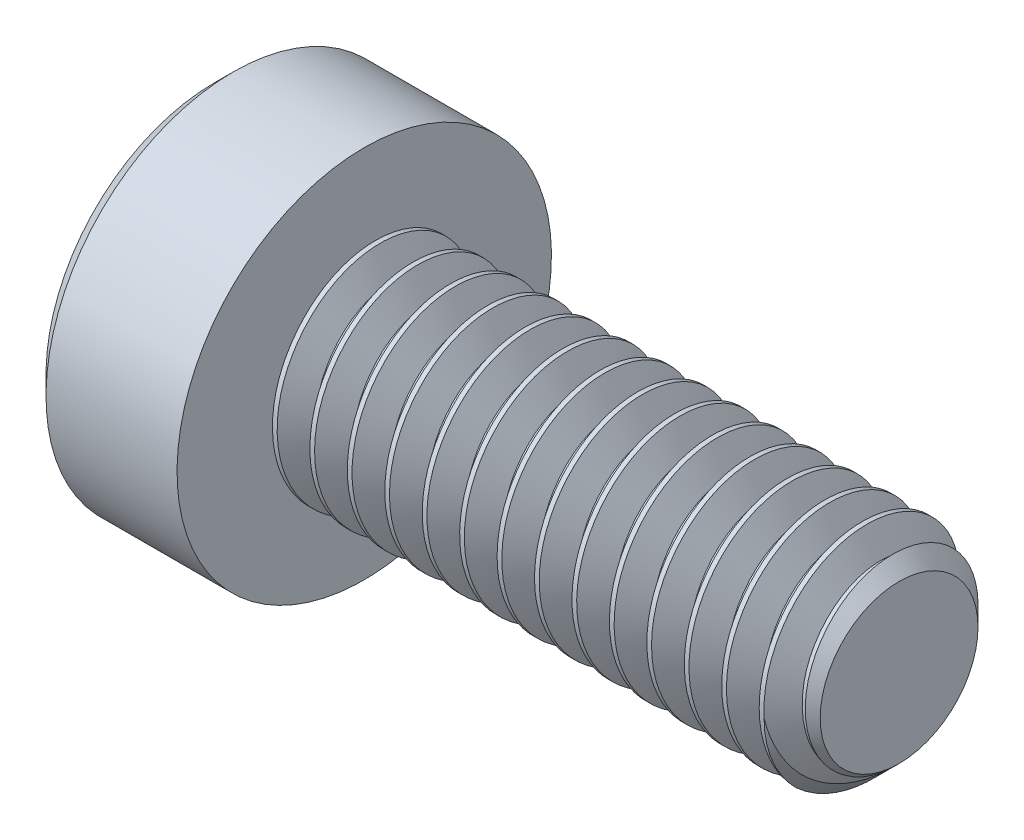
SolidWorks part; units mm, degrees
ref_plane "Front Plane" through (0, 0, 0) normal (0, 0, 1) x (1, 0, 0)
ref_plane "Top Plane" through (0, 0, 0) normal (0, 1, 0) x (1, 0, 0)
ref_plane "Right Plane" through (0, 0, 0) normal (1, 0, 0) x (0, 0, -1)
sketch "Sketch1" plane through (0, 0, 0) normal (0, 0, 1) x (1, 0, 0)
  line L0 (5, 0) -> (-5, 0) construction
  line L1 (5, 2) -> (5, -2) construction
  line L2 (-5, 3.5) -> (-5, -3.5) construction
  line L3 (-5, 3.5) -> (-7.45, 3.5) construction
  line L4 (-7.45, 3.5) -> (-7.8, 3.15) construction
  line L5 (-7.8, 3.15) -> (-7.8, -3.15) construction
  line L6 (-7.8, -3.15) -> (-7.45, -3.5) construction
  line L7 (-7.45, -3.5) -> (-5, -3.5) construction
  point P7 (-5.38, 0)
  point P12 (2.2, -2)
  dimension "D1" = 45
  dimension "Dec." = 4
  dimension "Length" = 10
  dimension "Head Dia" = 7
  dimension "Head Height" = 2.8
  dimension "Hex Depth" = 2.42
  dimension "Chamfer" = 0.35
  dimension "D2" = 2.8
ref_plane "Plane1" through (5, 0, 0) normal (1, 0, 0) x (0, 0, -1)
ref_plane "Plane2" through (-7.8, 0, 0) normal (1, 0, 0) x (0, 0, -1)
sketch "Sketch2" plane through (5, 0, 0) normal (1, 0, 0) x (0, 0, -1)
  circle A0 centre (0, 0) radius 2
extrude "Boss-Extrude1" add sketch "Sketch2" against normal up to vertex (10 mm away) up to point (-5, 0, 0)
sketch "Sketch3" plane through (5, 0, 0) normal (1, 0, 0) x (0, 0, -1)
  circle A0 centre (0, 0) radius 2 construction
  circle A1 centre (0, 0) radius 2
curve "Helix/Spiral1" pitch 0.7 height 10.67 radius 2 centre (5, 0, 0) axis (-1, 0, 0) start towards (0, 1, 0) parameters "Pitch"=0.7
chamfer "Chamfer1" distance 0.525 angle 45 1 edges at (5, 0, -2)
sketch "Sketch5" plane through (0, 0, 0) normal (0, 0, 1) x (1, 0, 0)
  line L0 (5, 2) -> (5.6125, 2)
  line L1 (5.6125, 2) -> (5.35, 1.5453)
  line L2 (5.35, 1.5453) -> (5.2625, 1.5453)
  line L3 (5.2625, 1.5453) -> (5, 2)
  line L4 (5.3063, 1.5453) -> (5.3063, 2) construction
  line L5 (5.1313, 1.7727) -> (5.4813, 1.7727) construction
  dimension "D1" = 60
  dimension "D2" = 0.35
  dimension "D3" = 0.0875
sweep "Cut-Sweep1" cut profiles "Sketch5" path "Helix/Spiral1" align with end faces yes
sketch "Sketch4" plane through (-7.8, 0, 0) normal (1, 0, 0) x (0, 0, -1)
  line L0 (-3.5, 0.7937) -> (3.5, 0.7937) construction
  line L1 (0, 1.4434) -> (-1.25, 0.7217)
  line L2 (-1.25, 0.7217) -> (-1.25, -0.7217)
  line L3 (-1.25, -0.7217) -> (0, -1.4434)
  line L4 (0, -1.4434) -> (1.25, -0.7217)
  line L5 (1.25, -0.7217) -> (1.25, 0.7217)
  line L6 (1.25, 0.7217) -> (0, 1.4434)
  line L7 (0, 0) -> (0, 0.7937) construction
  circle A0 centre (0, 0) radius 1.25 construction
  dimension "Hex Size" = 2.5
  dimension "D1" = 7
  dimension "D2" = 0.7937
sketch "Sketch6" plane through (0, 0, 0) normal (0, 0, 1) x (1, 0, 0)
  line L0 (-7.45, 3.5) -> (-7.8, 3.15) construction
  line L1 (-5, 3.5) -> (-7.45, 3.5) construction
  line L2 (-5, 3.5) -> (-5, -3.5) construction
  line L3 (-7.8, 3.15) -> (-7.8, -3.15) construction
  line L4 (-7.45, 3.5) -> (-7.8, 3.15)
  line L5 (-5, 3.5) -> (-7.45, 3.5)
  line L6 (-5, 3.5) -> (-5, 0)
  line L7 (-7.8, 3.15) -> (-7.8, 0)
  line L8 (-5, 0) -> (-7.8, 0) construction
  line L9 (-5, 0) -> (-7.8, 0)
revolve "Revolve1" add sketch "Sketch6" angle 360 about L8
extrude "Cut-Extrude1" cut sketch "Sketch4" along normal up to vertex (2.42 mm away) up to point (-5.38, 0, 0)
sketch "Sketch8" plane through (-7.8, 0, 0) normal (-1, 0, 0) x (0, 0, 1)
  circle A1 centre (0, 0) radius 1.4434
extrude "Cut-Extrude2" cut sketch "Sketch8" against normal through all draft 45
equation "\"D3@Helix/Spiral1\" = \"Length@Sketch1\"+\"Pitch@Helix/Spiral1\"-.03"
equation "\"D3@Sketch5\" = \"Pitch@Helix/Spiral1\"*.125"
equation "\"D2@Sketch5\" = \"Pitch@Helix/Spiral1\"*.50"
equation "\"D1@Chamfer1\" = \"Pitch@Helix/Spiral1\"*.75"
equation "\"D2@Sketch1\" = \"Pitch@Helix/Spiral1\"*4"
equation "\"D1@Sketch4\" = \"Head Dia@Sketch1\""
equation "\"Chamfer@Sketch1\" = \"Head Height@Sketch1\"/8"
